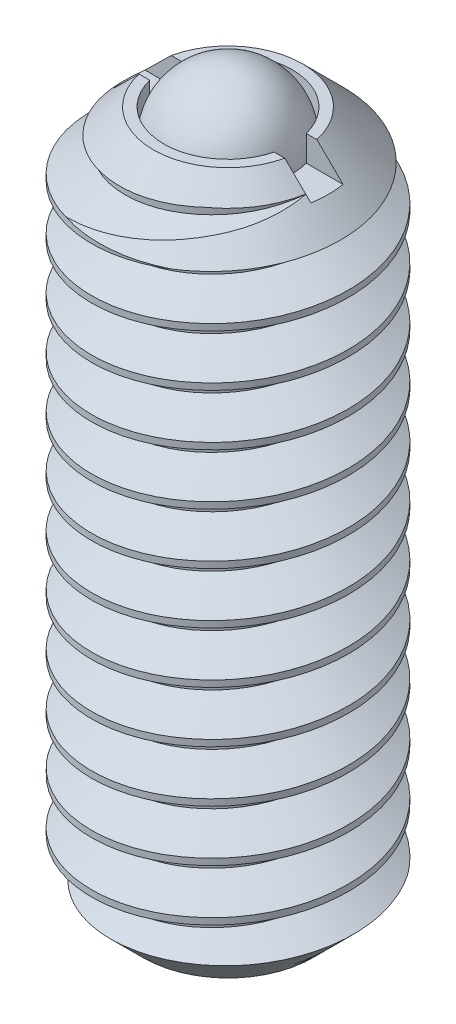
SolidWorks part; units mm, degrees
material "Plain Carbon Steel"
ref_plane "Front" through (0, 0, 0) normal (0, 0, 1) x (1, 0, 0)
ref_plane "Top" through (0, 0, 0) normal (0, 1, 0) x (1, 0, 0)
ref_plane "Right" through (0, 0, 0) normal (1, 0, 0) x (0, 0, -1)
sketch "Sketch24" plane through (0, 0, 0) normal (1, 0, 0) x (0, 0, -1)
  line L0 (3.175, 8.5725) -> (-3.175, 8.5725) construction
  line L1 (0, 8.5725) -> (3.175, 8.5725)
  line L2 (0, 8.5725) -> (0, -8.5725)
  line L3 (0, -8.5725) -> (3.175, -8.5725)
  line L4 (3.175, 8.5725) -> (3.175, -8.5725)
  point P5 (3.175, 2.8575)
  dimension "Body Length" = 17.145
  dimension "Screw Dia" = 6.35
  dimension "D1" = 5.715
revolve "Revolve1" add sketch "Sketch24" angle 360 about L2
sketch "Sketch37" plane through (0, 8.5725, 0) normal (0, 1, 0) x (1, 0, 0)
  circle A1 centre (0, 0) radius 3.175
  circle A2 centre (0, 0) radius 3.175
  dimension "D1" = 0
curve "Helix/Spiral1" pitch 1.27 height 18.415 turns 14.5 parameters "pitch"=1.27
sketch "Sketch38" plane through (0, 0, 0) normal (1, 0, 0) x (0, 0, -1)
  line L0 (-3.175, 9.6838) -> (-3.175, 8.5725)
  line L1 (-3.175, 9.6838) -> (-2.3501, 9.2075)
  line L2 (-2.3501, 9.2075) -> (-2.3501, 9.0488)
  line L3 (-2.3501, 9.0488) -> (-3.175, 8.5725)
  line L4 (-2.3501, 9.1281) -> (-3.175, 9.1281) construction
  line L5 (-2.7626, 9.4456) -> (-2.7626, 8.8106) construction
  line L6 (3.175, 8.5725) -> (-3.175, 8.5725) construction
  line L7 (0, 0) -> (0, 8.5725) construction
  dimension "D2" = 0.635
  dimension "D1" = 0.1588
  dimension "D3" = 60
  dimension "D4" = 0.8249
  dimension "D5" = 2.3501
  dimension "D6" = 0.4124
sweep "Cut-Sweep1" cut profiles "Sketch38" path "Helix/Spiral1" align with end faces yes
sketch "Sketch26" plane through (0, 0, 0) normal (1, 0, 0) x (0, 0, -1)
  line L0 (0, -6.5659) -> (0, 8.5725)
  line L1 (0, 8.5725) -> (0, -8.5725) construction
  line L2 (0, 8.5725) -> (1.5875, 8.5725)
  line L3 (1.5875, 8.5725) -> (1.5875, -6.5659)
  line L5 (1.5875, -6.5659) -> (0, -6.5659)
  line L7 (1.5875, 8.5725) -> (-1.5875, 8.5725) construction
  line L8 (3.175, 8.5725) -> (-3.175, 8.5725) construction
  dimension "D1" = 2.0066
  dimension "Ball Dia" = 3.175
revolve "Cut-Revolve10" cut sketch "Sketch26" angle 360 about L0
sketch "Sketch31" plane through (0, 0, 0) normal (1, 0, 0) x (0, 0, -1)
  line L0 (3.175, -8.5725) -> (2.0955, -8.5725)
  line L1 (3.175, 8.5725) -> (3.175, -8.5725) construction
  line L3 (0, 0) -> (0, -14.5366) construction
  line L4 (2.0955, -8.5725) -> (3.175, -7.493)
  line L5 (0, 0) -> (3.175, 0) construction
  line L14 (3.175, 8.5725) -> (1.8415, 8.5725)
  line L15 (0, 8.5725) -> (3.175, 8.5725) construction
  line L16 (1.8415, 8.5725) -> (3.175, 7.239)
  line L17 (3.175, 7.239) -> (3.175, 8.5725)
  line L18 (3.175, -7.493) -> (3.175, -8.5725)
  dimension "D1" = 0.254
  dimension "D2" = 45
  dimension "D3" = 0.254
revolve "Cut-Revolve13" cut sketch "Sketch31" angle 360 about L2
sketch "Sketch28" plane through (0, 0, 0) normal (1, 0, 0) x (0, 0, -1)
  line L0 (-3.175, -7.9375) -> (0.3969, -7.9375) construction
  line L1 (-0.3969, -8.5725) -> (0.3969, -8.5725) construction
  line L2 (-0.3969, -8.5725) -> (-0.3969, -7.9375) construction
  line L3 (-0.3969, -7.9375) -> (0.3969, -7.9375) construction
  line L4 (0.3969, -8.5725) -> (0.3969, -7.9375) construction
  line L5 (3.175, 8.5725) -> (-3.175, 8.5725) construction
  line L6 (-0.3969, 8.5725) -> (0.3969, 8.5725)
  line L7 (-0.3969, 8.5725) -> (-0.3969, 7.9375)
  line L8 (-0.3969, 7.9375) -> (0.3969, 7.9375)
  line L9 (0.3969, 8.5725) -> (0.3969, 7.9375)
  line L11 (-2.0955, -8.5725) -> (2.0955, -8.5725) construction
  dimension "D1" = 0.7937
  dimension "D2" = 0.635
extrude "Cut-Extrude11" cut sketch "Sketch28" against normal through all and the other way through all
sketch "Sketch27" plane through (0, 0, 0) normal (1, 0, 0) x (0, 0, -1)
  line L0 (0, 8.5725) -> (0, -8.5725) construction
  line L1 (1.5875, 8.5725) -> (1.5875, -6.5659) construction
  line L2 (0, -8.5725) -> (0, 6.2865) construction
  line L3 (0, 9.4615) -> (0, 6.2865)
  circle A0 centre (0, 7.874) radius 1.5875 construction
  arc A1 (0, 9.4615) -> (0, 6.2865) centre (0, 7.874) cw
  dimension "Ball Projection" = 0.889
revolve "Revolve2" add sketch "Sketch27" angle 360 about L3
ref_plane "Plane1" [suppressed] through (-7.9375, 0, 0) normal (1, 0, 0) x (0, 0, -1)
sketch "Sketch21" [suppressed] plane through (-7.9375, 0, 0) normal (1, 0, 0) x (0, 0, -1)
  line L0 (0, -1.7183) -> (0, -3.2804) construction
  line L2 (7.9375, 15.875) -> (-7.9375, 15.875) construction
  line L3 (0, 15.875) -> (0, -15.875) construction
  ellipse E0 centre (0, 2.3532) end of major axis (0, -2.8062) minor radius 3.9688
  dimension "D5" = 3.175
  dimension "D6" = 4.1275
  dimension "D7" = 4.5994
sketch "Sketch41" [suppressed] plane through (-7.9375, 0, 0) normal (1, 0, 0) x (0, 0, -1)
  ellipse E1 centre (0, 2.3532) end of major axis (0, 7.5125) minor radius 3.9688
  ellipse E2 centre (0, 2.3532) end of major axis (0, 7.5125) minor radius 3.9688
  dimension "D1" = 0
sketch "Sketch43" [suppressed] plane through (0, 0, 0) normal (1, 0, 0) x (0, 0, -1)
  ellipse E1 centre (0, 2.3532) end of major axis (0, 7.5125) minor radius 3.9688
  ellipse E2 centre (0, 2.3532) end of major axis (0, 7.5125) minor radius 3.9688
  dimension "D1" = 0
extrude "Extrude9" [suppressed] cut sketch "Sketch43" against normal through all
sketch "Sketch44" [suppressed] plane through (0, 0, 0) normal (1, 0, 0) x (0, 0, -1)
  ellipse E1 centre (0, 2.3532) end of major axis (0, 7.5125) minor radius 3.9688
  ellipse E2 centre (0, 2.3532) end of major axis (0, 7.5125) minor radius 3.9688
  dimension "D1" = 0
extrude "Extrude10" [suppressed] add sketch "Sketch44" against normal blind 2.3501 separate body
dome "Dome1" [suppressed] faces to dome 1 distance 0.4124 parameters "D1"=0.4124
sketch "Sketch45" plane through (0, 0, 0) normal (0, 1, 0) x (1, 0, 0)
  circle A0 centre (0, 0) radius 1.5875
  arc A1 (-1.5371, -0.3969) -> (1.5371, -0.3969) centre (0, 0) ccw construction
extrude "Extrude11" [suppressed] cut sketch "Sketch45" against normal through all and the other way through all
sketch "Sketch46" plane through (0, -8.5725, 0) normal (0, -1, 0) x (1, 0, 0)
  line L1 (-1.0033, 0.5793) -> (-1.0033, -0.5793)
  line L2 (-1.0033, -0.5793) -> (0, -1.1585)
  line L3 (0, -1.1585) -> (1.0033, -0.5793)
  line L4 (1.0033, -0.5793) -> (1.0033, 0.5793)
  line L5 (1.0033, 0.5793) -> (0, 1.1585)
  line L6 (0, 1.1585) -> (-1.0033, 0.5793)
  circle A0 centre (0, 0) radius 1.0033 construction
  dimension "Hex" = 2.0066
extrude "Extrude12" cut sketch "Sketch46" against normal blind 1.0033
sketch "Sketch47" plane through (0, -8.5725, 0) normal (0, -1, 0) x (1, 0, 0)
  circle A0 centre (0, 0) radius 1.1585
extrude "Extrude13" cut sketch "Sketch47" against normal blind 1.0033 draft 60
equation "\"D1@Sketch26\" = \"Hex@Sketch46\""
equation "\"D1@Sketch28\" = \"Screw Dia@Sketch24\"/8"
equation "\"D1@Sketch38\" = \"pitch@Helix/Spiral1\"*.125"
equation "\"D2@Sketch38\" = \"pitch@Helix/Spiral1\"*.50"
equation "\"D3@Helix/Spiral1\" = \"Body Length@Sketch24\"+\"pitch@Helix/Spiral1\""
equation "\"D5@Sketch21\" = \"Screw Dia@Sketch24\"*.50"
equation "\"D6@Sketch21\" = \"D5@Sketch21\"*1.3"
equation "\"D7@Sketch21\" = \"pitch@Helix/Spiral1\"*3.62154"
equation "\"D1@Sketch24\" = \"pitch@Helix/Spiral1\"*4.50"
equation "\"D1@Plane1\" = \"Screw Dia@Sketch24\"/2"
equation "\"D1@Extrude10\" = \"D5@Sketch38\""
equation "\"D1@Dome1\" = \"D6@Sketch38\""
equation "\"D2@Sketch28\" = \"pitch@Helix/Spiral1\"/2"
equation "\"D1@Extrude12\" = \"Hex@Sketch46\"/2"
equation "\"D1@Extrude13\" = \"Hex@Sketch46\"/2"
